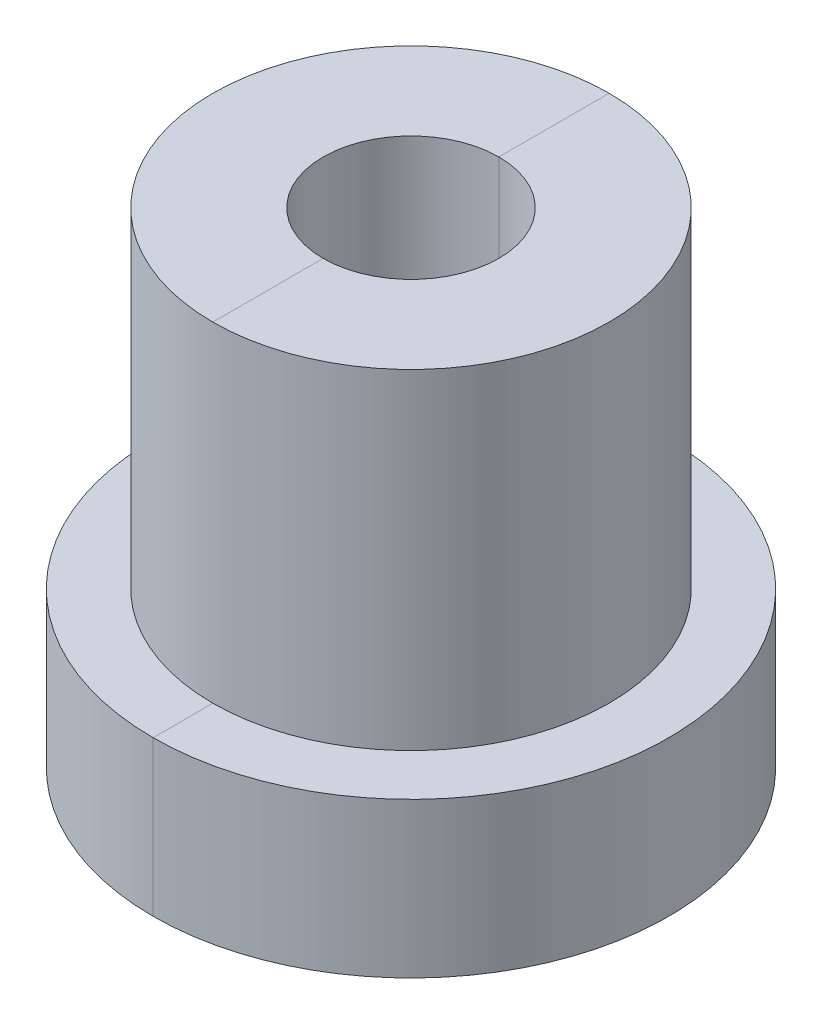
SolidWorks part; units mm, degrees
ref_plane "Front Plane" through (0, 0, 0) normal (0, 0, 1) x (1, 0, 0)
ref_plane "Top Plane" through (0, 0, 0) normal (0, 1, 0) x (1, 0, 0)
ref_plane "Right Plane" through (0, 0, 0) normal (1, 0, 0) x (0, 0, -1)
sketch "Sketch1" plane through (0, 0, 0) normal (0, 1, 0) x (1, 0, 0)
  circle A0 centre (0, 0) radius 7.9375
  dimension "D1" = 15.875
extrude "Boss-Extrude1" add sketch "Sketch1" along normal blind 4.7625
sketch "Sketch2" plane through (0, 4.7625, 0) normal (0, 1, 0) x (1, 0, 0)
  circle A0 centre (0, 0) radius 6.35
  dimension "D1" = 12.7
extrude "Boss-Extrude2" add sketch "Sketch2" along normal blind 10.16
sketch "Sketch4" plane through (0, 14.9225, 0) normal (0, 1, 0) x (1, 0, 0)
  circle A0 centre (0, 0) radius 6.1
  circle A1 centre (0, 0) radius 6.35
  circle A2 centre (0, 0) radius 6.35
  dimension "D2" = 0.25
  dimension "D1" = 0
extrude "Cut-Extrude2" cut sketch "Sketch4" against normal up to surface (10.16 mm away) up to face at (0, 4.7625, 6.35)
sketch "Sketch3" plane through (0, 14.9225, 0) normal (0, 1, 0) x (1, 0, 0)
  circle A0 centre (0, 0) radius 2.7051
  dimension "D1" = 5.4102
extrude "Cut-Extrude1" cut sketch "Sketch3" against normal through all
split line "Split Line1"
